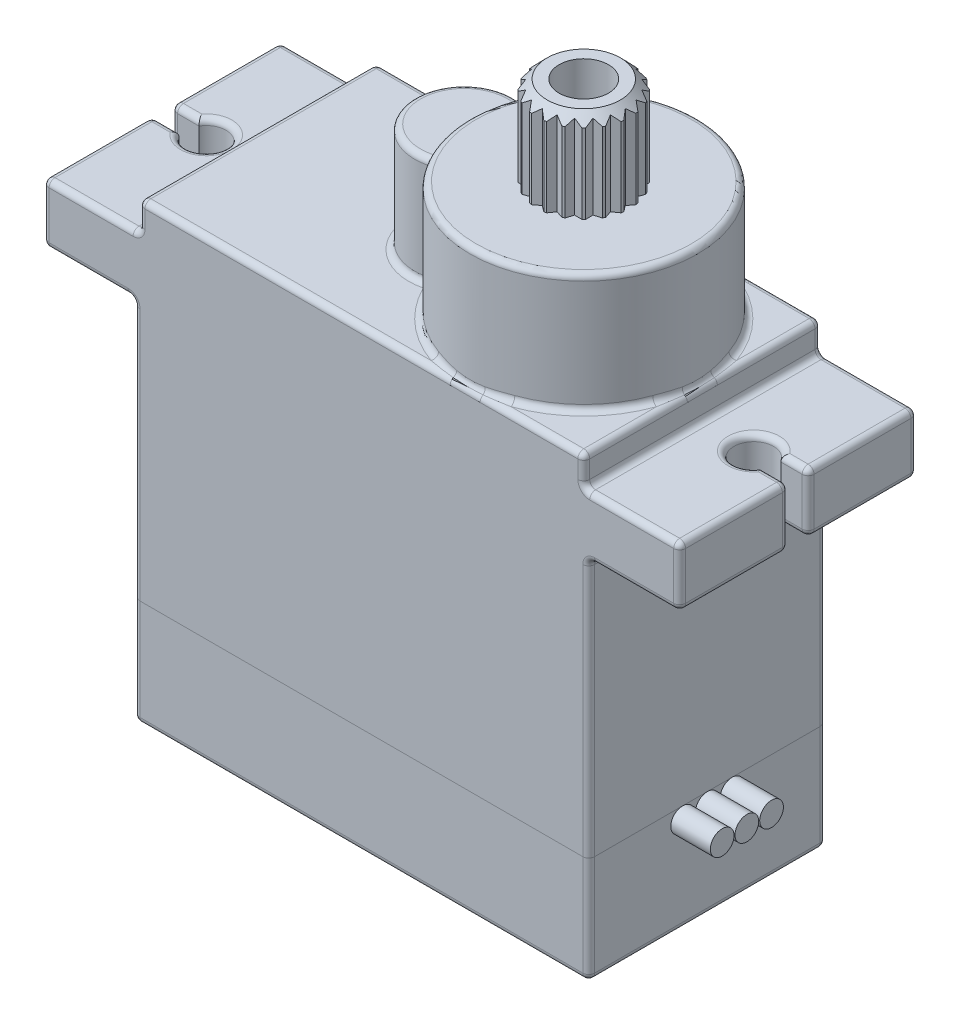
SolidWorks part; units mm, degrees
ref_plane "Front Plane" through (0, 0, 0) normal (0, 0, 1) x (1, 0, 0)
ref_plane "Top Plane" through (0, 0, 0) normal (0, 1, 0) x (1, 0, 0)
ref_plane "Right Plane" through (0, 0, 0) normal (1, 0, 0) x (0, 0, -1)
sketch "Sketch1" plane through (0, 0, 0) normal (0, 1, 0) x (1, 0, 0)
  line L1 (-11.5, -6) -> (11.5, -6)
  line L2 (-11.5, -6) -> (-11.5, 6)
  line L3 (-11.5, 6) -> (11.5, 6)
  line L4 (11.5, -6) -> (11.5, 6)
  line L5 (-11.5, -6) -> (11.5, 6) construction
  line L6 (-11.5, 6) -> (11.5, -6) construction
  point P0 (0, 0)
  dimension "D1" = 12
  dimension "D2" = 23
extrude "Boss-Extrude1" add sketch "Sketch1" along normal blind 18.5
sketch "Sketch2" plane through (0, 18.5, 0) normal (0, 1, 0) x (1, 0, 0)
  line L0 (11.5, 6) -> (-11.5, 6) construction
  line L1 (-16.1, -6) -> (16.1, -6)
  line L2 (-16.1, -6) -> (-16.1, 6)
  line L3 (-16.1, 6) -> (16.1, 6)
  line L4 (16.1, -6) -> (16.1, 6)
  line L5 (-16.1, -6) -> (16.1, 6) construction
  line L6 (-16.1, 6) -> (16.1, -6) construction
  point P0 (0, 0)
  dimension "D1" = 32.2
extrude "Boss-Extrude2" add sketch "Sketch2" along normal blind 3
sketch "Sketch3" plane through (0, 21.5, 0) normal (0, 1, 0) x (1, 0, 0)
  line L0 (16.1, 6) -> (-16.1, 6) construction
  line L1 (-11.25, -6) -> (11.25, -6)
  line L2 (-11.25, -6) -> (-11.25, 6)
  line L3 (-11.25, 6) -> (11.25, 6)
  line L4 (11.25, -6) -> (11.25, 6)
  line L5 (-11.25, -6) -> (11.25, 6) construction
  line L6 (-11.25, 6) -> (11.25, -6) construction
  point P0 (0, 0)
  dimension "D1" = 22.5
extrude "Boss-Extrude3" add sketch "Sketch3" along normal blind 1.5
sketch "Sketch4" plane through (0, 23, 0) normal (0, 1, 0) x (1, 0, 0)
  line L0 (-11.25, 6) -> (-11.25, -6) construction
  line L1 (5.25, 5.75) -> (5.25, 6) construction
  line L2 (11.25, 6) -> (-11.25, 6) construction
  line L3 (11, 0) -> (11.25, 0) construction
  line L4 (11.25, -6) -> (11.25, 6) construction
  line L5 (5.25, -5.75) -> (5.25, -6) construction
  line L6 (-11.25, -6) -> (11.25, -6) construction
  circle A0 centre (5.25, 0) radius 5.75
  point P5 (-11.25, 0)
  dimension "D1" = 11.5
extrude "Boss-Extrude4" add sketch "Sketch4" along normal blind 6
sketch "Sketch5" plane through (0, 23, 0) normal (0, 1, 0) x (1, 0, 0)
  line L0 (-11.25, 6) -> (-11.25, -6) construction
  circle A0 centre (-0.8, 0) radius 2.5
  circle A1 centre (5.25, 0) radius 5.75 construction
  circle A2 centre (5.25, 0) radius 5.75 construction
  point P2 (-3.3, 0)
  point P5 (-11.25, 0)
  point P6 (11, 0)
  dimension "D1" = 5
  dimension "D2" = 14.3
extrude "Boss-Extrude5" add sketch "Sketch5" along normal blind 5.5
sketch "Sketch6" plane through (0, 21.5, 0) normal (0, 1, 0) x (1, 0, 0)
  line L0 (-11.25, 6) -> (-11.25, -6) construction
  line L1 (0, 6) -> (0, -6) construction
  line L2 (11.25, 6) -> (-11.25, 6) construction
  line L3 (-11.25, -6) -> (11.25, -6) construction
  line L4 (-14.716, 0.5) -> (-16.1, 0.5)
  line L5 (-16.1, 6) -> (-16.1, -6) construction
  line L6 (-14.716, -0.5) -> (-16.1, -0.5)
  line L7 (-16.1, 0.5) -> (-16.1, -0.5)
  line L8 (16.1, 0.5) -> (16.1, -0.5)
  line L9 (14.716, -0.5) -> (16.1, -0.5)
  line L10 (14.716, 0.5) -> (16.1, 0.5)
  arc A0 (-14.716, -0.5) -> (-14.716, 0.5) centre (-13.85, 0) ccw
  arc A1 (14.716, -0.5) -> (14.716, 0.5) centre (13.85, 0) cw
  point P4 (-11.25, 0)
  dimension "D1" = 2
  dimension "D2" = 27.7
  dimension "D3" = 1
extrude "Cut-Extrude1" cut sketch "Sketch6" against normal through all
sketch "Sketch7" plane through (0, 29, 0) normal (0, 1, 0) x (1, 0, 0)
  circle A0 centre (5.25, 0) radius 2.35
  dimension "D1" = 4.7
extrude "Boss-Extrude6" add sketch "Sketch7" along normal blind 4.5
sketch "Sketch8" plane through (11.5, 0, 0) normal (1, 0, 0) x (0, 0, -1)
  line L0 (-1.25, 4.8) -> (1.25, 4.8) construction
  line L1 (-6, 0) -> (6, 0) construction
  circle A0 centre (-1.25, 4.8) radius 0.6
  circle A1 centre (0, 4.8) radius 0.6
  circle A2 centre (1.25, 4.8) radius 0.6
  dimension "D1" = 1.2
  dimension "D2" = 4.8
  dimension "D3" = 2.5
extrude "Boss-Extrude8" add sketch "Sketch8" along normal blind 2
fillet "Fillet1" radius 0.3 56 edges at (11.5, 0, 0) (11.5, 18.5, 0) (15.408, 18.5, 0.5) (12.85, 18.5, 0) (15.408, 18.5, -0.5) (15.408, 21.5, 0.5) (15.408, 21.5, -0.5) (12.85, 21.5, 0) (-11.25, 23, 0) (-15.408, 21.5, -0.5) (-11.25, 21.5, 0) (-15.408, 21.5, 0.5) (-12.85, 21.5, 0) (-16.1, 20, 0.5) (-16.1, 21.5, 3.25) (-16.1, 21.5, -3.25) (-16.1, 20, -0.5) (-16.1, 18.5, 3.25) (-16.1, 18.5, -3.25) (-15.408, 18.5, -0.5) (-12.85, 18.5, 0) (-15.408, 18.5, 0.5) (-11.5, 18.5, 0) (-11.5, 0, 0) (11.25, 23, 0) (11.25, 21.5, 0) (16.1, 21.5, 3.25) (16.1, 20, 0.5) (16.1, 18.5, 3.25) (16.1, 18.5, -3.25) (16.1, 20, -0.5) (16.1, 21.5, -3.25) (11.5, 9.25, -6) (13.8, 18.5, -6) (16.1, 20, -6) (13.675, 21.5, -6) (11.25, 22.25, -6) (0, 23, -6) (-11.25, 22.25, -6) (-13.675, 21.5, -6) (-16.1, 20, -6) (-13.8, 18.5, -6) (-11.5, 9.25, -6) (0, 0, -6) (-11.5, 9.25, 6) (-13.8, 18.5, 6) (-16.1, 20, 6) (-13.675, 21.5, 6) (-11.25, 22.25, 6) (0, 23, 6) (11.25, 22.25, 6) (13.675, 21.5, 6) (16.1, 20, 6) (13.8, 18.5, 6) (11.5, 9.25, 6) (0, 0, 6)
fillet "Fillet2" radius 0.3 10 edges at (5.25, 23, 5.75) (9.3159, 23, 4.0659) (11, 23, 0) (9.3159, 23, -4.0659) (5.25, 23, -5.75) (-3.3, 23, 0) (1.8189, 23, 4.6141) (1.8189, 23, -4.6141) (5.25, 29, 5.75) (-3.3, 28.5, 0)
chamfer "Chamfer1" distance 0.5 angle 45 1 edges at (5.25, 33.5, 2.35)
sketch "Sketch10" plane through (0, 33.5, 0) normal (0, 1, 0) x (1, 0, 0)
  line L0 (5.25, 0) -> (4.9433, 2.3299) construction
  line L1 (5.25, 0) -> (5.5567, 2.3299) construction
  line L2 (5.25, 0) -> (5.25, 2.35) construction
  line L3 (4.9433, 2.3299) -> (5.25, 2.1)
  line L4 (5.25, 2.1) -> (5.5567, 2.3299)
  line L5 (5.8989, 1.9972) -> (6.2617, 2.1211)
  line L6 (5.6783, 2.3106) -> (5.8989, 1.9972)
  line L7 (6.4843, 1.6989) -> (6.8676, 1.7046)
  line L8 (6.3713, 2.0652) -> (6.4843, 1.6989)
  line L9 (6.9489, 1.2343) -> (7.3152, 1.1213)
  line L10 (6.9546, 1.6176) -> (6.9489, 1.2343)
  line L11 (7.2472, 0.6489) -> (7.5606, 0.4283)
  line L12 (7.3711, 1.0117) -> (7.2472, 0.6489)
  line L13 (7.35, 0) -> (7.5799, -0.3067)
  line L14 (7.5799, 0.3067) -> (7.35, 0)
  line L15 (7.2472, -0.6489) -> (7.3711, -1.0117)
  line L16 (7.5606, -0.4283) -> (7.2472, -0.6489)
  line L17 (6.9489, -1.2343) -> (6.9546, -1.6176)
  line L18 (7.3152, -1.1213) -> (6.9489, -1.2343)
  line L19 (6.4843, -1.6989) -> (6.3713, -2.0652)
  line L20 (6.8676, -1.7046) -> (6.4843, -1.6989)
  line L21 (5.8989, -1.9972) -> (5.6783, -2.3106)
  line L22 (6.2617, -2.1211) -> (5.8989, -1.9972)
  line L23 (5.25, -2.1) -> (4.9433, -2.3299)
  line L24 (5.5567, -2.3299) -> (5.25, -2.1)
  line L25 (4.6011, -1.9972) -> (4.2383, -2.1211)
  line L26 (4.8217, -2.3106) -> (4.6011, -1.9972)
  line L27 (4.0157, -1.6989) -> (3.6324, -1.7046)
  line L28 (4.1287, -2.0652) -> (4.0157, -1.6989)
  line L29 (3.5511, -1.2343) -> (3.1848, -1.1213)
  line L30 (3.5454, -1.6176) -> (3.5511, -1.2343)
  line L31 (3.2528, -0.6489) -> (2.9394, -0.4283)
  line L32 (3.1289, -1.0117) -> (3.2528, -0.6489)
  line L33 (3.15, 0) -> (2.9201, 0.3067)
  line L34 (2.9201, -0.3067) -> (3.15, 0)
  line L35 (3.2528, 0.6489) -> (3.1289, 1.0117)
  line L36 (2.9394, 0.4283) -> (3.2528, 0.6489)
  line L37 (3.5511, 1.2343) -> (3.5454, 1.6176)
  line L38 (3.1848, 1.1213) -> (3.5511, 1.2343)
  line L39 (4.0157, 1.6989) -> (4.1287, 2.0652)
  line L40 (3.6324, 1.7046) -> (4.0157, 1.6989)
  line L41 (4.6011, 1.9972) -> (4.8217, 2.3106)
  line L42 (4.2383, 2.1211) -> (4.6011, 1.9972)
  circle A0 centre (5.25, 0) radius 2.35 construction
  arc A1 (5.5567, 2.3299) -> (4.9433, 2.3299) centre (5.25, 0) ccw
  circle A2 centre (5.25, 0) radius 2.1 construction
  arc A3 (6.2617, 2.1211) -> (5.6783, 2.3106) centre (5.25, 0) ccw
  arc A4 (6.8676, 1.7046) -> (6.3713, 2.0652) centre (5.25, 0) ccw
  arc A5 (7.3152, 1.1213) -> (6.9546, 1.6176) centre (5.25, 0) ccw
  arc A6 (7.5606, 0.4283) -> (7.3711, 1.0117) centre (5.25, 0) ccw
  arc A7 (7.5799, -0.3067) -> (7.5799, 0.3067) centre (5.25, 0) ccw
  arc A8 (7.3711, -1.0117) -> (7.5606, -0.4283) centre (5.25, 0) ccw
  arc A9 (6.9546, -1.6176) -> (7.3152, -1.1213) centre (5.25, 0) ccw
  arc A10 (6.3713, -2.0652) -> (6.8676, -1.7046) centre (5.25, 0) ccw
  arc A11 (5.6783, -2.3106) -> (6.2617, -2.1211) centre (5.25, 0) ccw
  arc A12 (4.9433, -2.3299) -> (5.5567, -2.3299) centre (5.25, 0) ccw
  arc A13 (4.2383, -2.1211) -> (4.8217, -2.3106) centre (5.25, 0) ccw
  arc A14 (3.6324, -1.7046) -> (4.1287, -2.0652) centre (5.25, 0) ccw
  arc A15 (3.1848, -1.1213) -> (3.5454, -1.6176) centre (5.25, 0) ccw
  arc A16 (2.9394, -0.4283) -> (3.1289, -1.0117) centre (5.25, 0) ccw
  arc A17 (2.9201, 0.3067) -> (2.9201, -0.3067) centre (5.25, 0) ccw
  arc A18 (3.1289, 1.0117) -> (2.9394, 0.4283) centre (5.25, 0) ccw
  arc A19 (3.5454, 1.6176) -> (3.1848, 1.1213) centre (5.25, 0) ccw
  arc A20 (4.1287, 2.0652) -> (3.6324, 1.7046) centre (5.25, 0) ccw
  arc A21 (4.8217, 2.3106) -> (4.2383, 2.1211) centre (5.25, 0) ccw
  point P114 (5.25, 0)
  dimension "D1" = 4.2
  dimension "D2" = 15
  dimension "D3" = 20
extrude "Cut-Extrude2" cut sketch "Sketch10" against normal up to surface (4.5 mm away) contours L41 A21 L42 | L39 A20 L40 | L37 A19 L38 | L35 A18 L36 | L33 A17 L34 | L31 A16 L32 | L29 A15 L30 | L27 A14 L28 | L25 A13 L26 | L23 A12 L24 | L21 A11 L22 | L19 A10 L20 | L17 A9 L18 | L15 A8 L16 | L13 A7 L14 | L11 A6 L12 | L9 A5 L10 | L7 A4 L8 | L5 A3 L6 | L4 A1 L3 up to face at (5.25, 29, 5.45)
ref_plane "Plane1" through (0, 5.4, 0) normal (0, 1, 0) x (1, 0, 0)
split line "Split Line1"
sketch "Sketch14" plane through (0, 33.5, 0) normal (0, 1, 0) x (1, 0, 0)
  circle A0 centre (5.25, 0) radius 1.25
  dimension "D1" = 2.5
extrude "Cut-Extrude3" cut sketch "Sketch14" against normal blind 2.5
